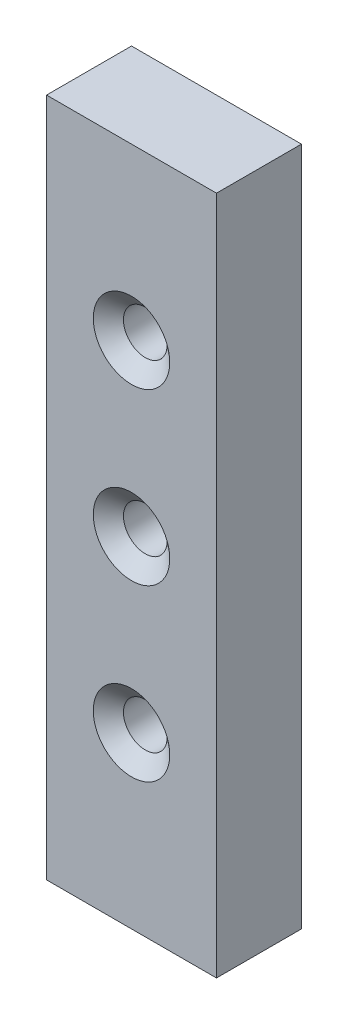
SolidWorks part; units mm, degrees
ref_plane "Front Plane" through (0, 0, 0) normal (0, 0, 1) x (1, 0, 0)
ref_plane "Top Plane" through (0, 0, 0) normal (0, 1, 0) x (1, 0, 0)
ref_plane "Right Plane" through (0, 0, 0) normal (1, 0, 0) x (0, 0, -1)
sketch "Sketch1" plane through (0, 0, 0) normal (0, 0, 1) x (1, 0, 0)
  line L1 (-6.35, 25.4) -> (6.35, 25.4)
  line L2 (-6.35, 25.4) -> (-6.35, -25.4)
  line L3 (-6.35, -25.4) -> (6.35, -25.4)
  line L4 (6.35, 25.4) -> (6.35, -25.4)
  dimension "D1" = 6.35
  dimension "D2" = 12.7
  dimension "D3" = 25.4
  dimension "D4" = 50.8
extrude "Boss-Extrude1" add sketch "Sketch1" along normal mid plane 6.35
sketch "Sketch5" plane through (0, 0, 3.175) normal (0, 0, 1) x (1, 0, 0)
  line L0 (6.35, 25.4) -> (-6.35, 25.4) construction
  line L1 (-6.35, 25.4) -> (-6.35, -25.4) construction
  point P0 (0, 12.7)
  point P11 (0, 0)
  point P12 (0, -12.7)
  dimension "D1" = 12.7
  dimension "D2" = 6.35
  dimension "D3" = 1
  dimension "D4" = 3
hole_wizard "CSK for #4 Flat Head Machine Screw (100)1" positions "Sketch7" profile "Sketch6" countersink size "#4" standard "ANSI Inch" end condition through all
sketch "Sketch7" plane through (0, 0, 3.175) normal (0, 0, 1) x (1, 0, 0)
  point P0 (0, 12.7)
  point P3 (0, 0)
  point P6 (0, -12.7)
sketch "Sketch6" plane through (0, 12.7, 3.175) normal (1, 0, 0) x (0, -1, 0)
  line L0 (0, 0) -> (0, 6.35)
  line L1 (0, 6.35) -> (1.6319, 6.35)
  line L2 (1.6319, 6.35) -> (1.6319, 1.0284)
  line L3 (1.6319, 1.0284) -> (2.8575, 0)
  line L5 (2.8575, 0) -> (0, 0)
  line L6 (-1.6319, 1.0284) -> (-2.8575, 0) construction
  line L11 (0, -6.35) -> (0, 107.95) construction
  dimension "Thru Hole Dia." = 3.2639
  dimension "Thru Hole Depth" = 6.35
  dimension "Near C'Sink Dia." = 5.715
  dimension "Near C'Sink Angle" = 100
